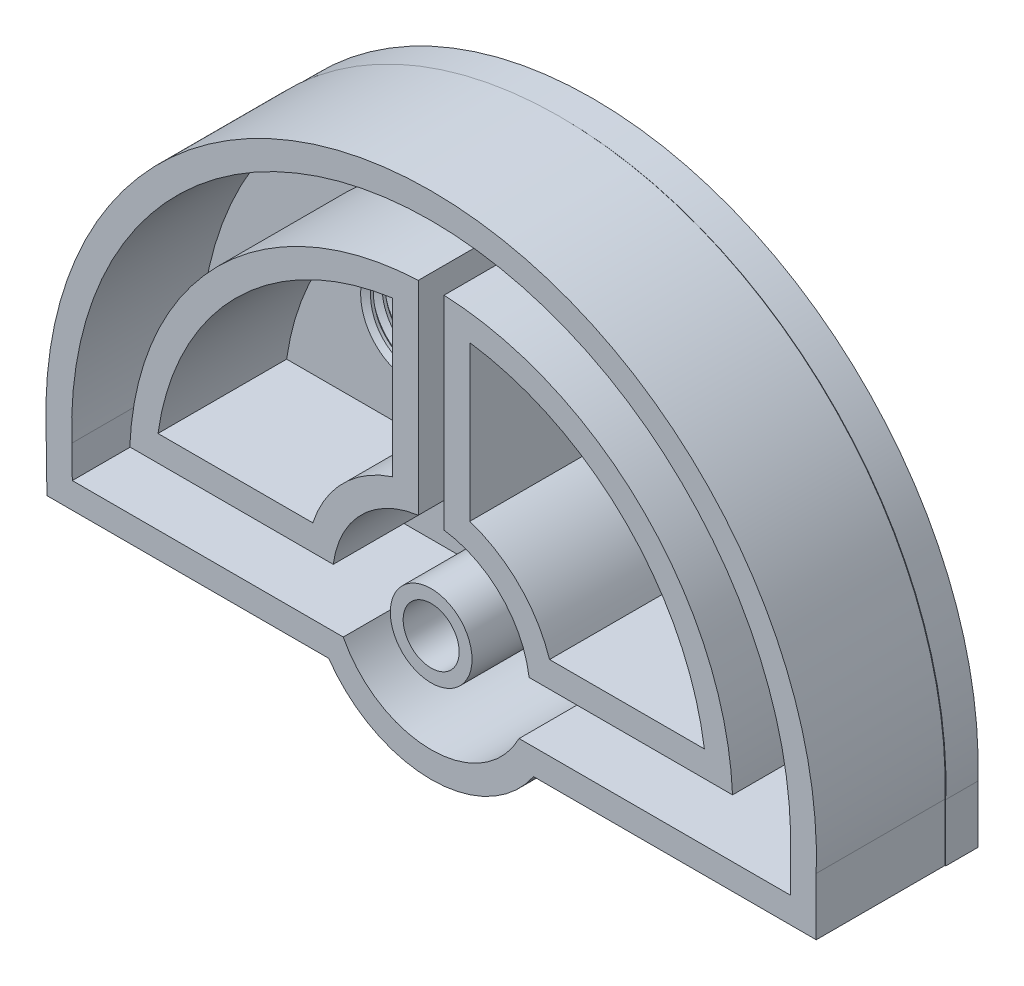
SolidWorks part; units mm, degrees
material "ABS"
ref_plane "Front Plane" through (0, 0, 0) normal (0, 0, 1) x (1, 0, 0)
ref_plane "Top Plane" through (0, 0, 0) normal (0, 1, 0) x (1, 0, 0)
ref_plane "Right Plane" through (0, 0, 0) normal (1, 0, 0) x (0, 0, -1)
sketch "Sketch1" plane through (0, 0, 0) normal (0, 0, 1) x (1, 0, 0)
  line L4 (7.9598, -5.4998) -> (29.9221, -5.5)
  line L5 (29.9221, -5.5) -> (29.9221, -1.0352)
  line L6 (-29.9216, -1.0497) -> (-29.8579, -5.4993)
  line L7 (-29.8579, -5.4993) -> (-7.9599, -5.4996)
  line L8 (-27.9221, -1) -> (-27.8863, -3.4994)
  line L9 (-27.8863, -3.4994) -> (-6.8307, -3.4996)
  line L10 (6.8306, -3.4998) -> (27.9221, -3.5)
  line L11 (27.9221, -3.5) -> (27.9221, -1)
  line L12 (-7.6096, 1) -> (-23.4187, 1)
  line L13 (7.6096, 1) -> (23.4187, 1)
  line L14 (1, 23.4187) -> (1, 7.6096)
  line L15 (-1, 23.4187) -> (-1, 7.6096)
  line L16 (-9.1981, 3) -> (-21.2291, 3)
  line L17 (-3, 21.2291) -> (-3, 9.1981)
  line L18 (3, 21.2291) -> (3, 9.1981)
  line L19 (9.1981, 3) -> (21.2291, 3)
  arc A3 (29.9221, -1.0352) -> (-29.9216, -1.0497) centre (0, 0) ccw
  arc A4 (-7.9599, -5.4996) -> (7.9598, -5.4998) centre (0, 0) ccw
  arc A5 (-3, 21.2291) -> (-21.2291, 3) centre (0, 0) ccw
  arc A6 (-3, 9.1981) -> (-9.1981, 3) centre (0, 0) ccw
  arc A7 (27.9221, -1) -> (-27.9221, -1) centre (0, 0) ccw
  circle A8 centre (0, 0) radius 3.175
  arc A9 (-6.8307, -3.4996) -> (6.8306, -3.4998) centre (0, 0) ccw
  arc A10 (-1, 7.6096) -> (-7.6096, 1) centre (0, 0) ccw
  arc A11 (7.6096, 1) -> (1, 7.6096) centre (0, 0) ccw
  arc A12 (23.4187, 1) -> (1, 23.4187) centre (0, 0) ccw
  arc A13 (-1, 23.4187) -> (-23.4187, 1) centre (0, 0) ccw
  arc A14 (9.1981, 3) -> (3, 9.1981) centre (0, 0) ccw
  arc A15 (21.2291, 3) -> (3, 21.2291) centre (0, 0) ccw
  circle A16 centre (0, 0) radius 2.175
  dimension "D1" = 2
  dimension "D2" = 2
  dimension "D3" = 1
extrude "Boss-Extrude1" add sketch "Sketch1" along normal blind 10 contours L7 A4 L4 L5 A3 L6 A9 L9 L8 A7 L11 L10 | L15 A13 L12 A10 L17 A6 L16 A5 | L13 A12 L14 A11 A15 L19 A14 L18 | A8 | A16 region at (-0.0001, -8.957, 0) region at (-15.5141, 1.317, 0) region at (5.6512, 5.6512, 0)
sketch "Sketch2" plane through (0, 0, 0) normal (0, 0, 1) x (1, 0, 0)
  line L4 (8.0235, -5.4995) -> (29.9858, -5.4998)
  line L5 (29.9858, -5.4998) -> (29.9858, -1.0349)
  line L6 (-29.8579, -1.0495) -> (-29.8579, -5.4993)
  line L7 (-29.8579, -5.4993) -> (-7.8962, -5.4993)
  arc A2 (29.9858, -1.0349) -> (-29.8579, -1.0495) centre (0.0637, 0.0003) ccw
  arc A3 (-7.8962, -5.4993) -> (8.0235, -5.4995) centre (0.0637, 0.0003) ccw
extrude "Boss-Extrude2" add sketch "Sketch2" against normal blind 2.5
sketch "Sketch3" plane through (0, 0, 0) normal (0, 0, 1) x (1, 0, 0)
  line L0 (0, 0) -> (0, 9.8757) construction
  line L2 (15.1604, 15.1604) -> (6.8413, 6.8413) construction
  arc A0 (21.2291, 3) -> (3, 21.2291) centre (0, 0) ccw construction
  arc A1 (9.1981, 3) -> (3, 9.1981) centre (0, 0) ccw construction
  circle A2 centre (11.0008, 11.0008) radius 3.9182
  circle A3 centre (-11.0008, 11.0008) radius 3.9182
  circle A4 centre (0, 0) radius 2.175
extrude "Cut-Extrude1" cut sketch "Sketch3" against normal blind 2.5
thread "Thread1" pitch 0.9071 method extrude profile "Thread Profile1" start angle 0, offset 0, length 2.5, pitch 0.9071, diameter 7.8365
ref_plane "Plane1" through (-7.0826, 11.0008, -2.5) normal (0, -1, 0) x (1, 0, 0)
sketch "Thread Profile1" plane through (-7.0826, 11.0008, -2.5) normal (0, -1, 0) x (1, 0, 0)
  line L0 (0, 0) -> (0, 0.9071) construction
  line L11 (0, 0) -> (0, 0.7937)
  line L12 (0, 0.7937) -> (-0.491, 0.5103)
  line L13 (-0.491, 0.5103) -> (-0.491, 0.2835)
  line L15 (-0.491, 0.2835) -> (0, 0)
  line L17 (-0.491, 0.3969) -> (0, 0.3969) construction
  point P2 (0, 0)
  dimension "Pitch" = 0.9071
  dimension "Profile_Angle" = 60
  dimension "Profile_Land" = 0.2268
  dimension "Profile_Height" = 0.491
thread "Thread2" pitch 0.9071 method extrude profile "Thread Profile2" start angle 0, offset 0, length 2.5, pitch 0.9071, diameter 7.8365
ref_plane "Plane2" through (14.919, 11.0008, -2.5) normal (0, -1, 0) x (1, 0, 0)
sketch "Thread Profile2" plane through (14.919, 11.0008, -2.5) normal (0, -1, 0) x (1, 0, 0)
  line L0 (0, 0) -> (0, 0.9071) construction
  line L11 (0, 0) -> (0, 0.7937)
  line L12 (0, 0.7937) -> (-0.491, 0.5103)
  line L13 (-0.491, 0.5103) -> (-0.491, 0.2835)
  line L15 (-0.491, 0.2835) -> (0, 0)
  line L17 (-0.491, 0.3969) -> (0, 0.3969) construction
  point P2 (0, 0)
  dimension "Pitch" = 0.9071
  dimension "Profile_Angle" = 60
  dimension "Profile_Land" = 0.2268
  dimension "Profile_Height" = 0.491
